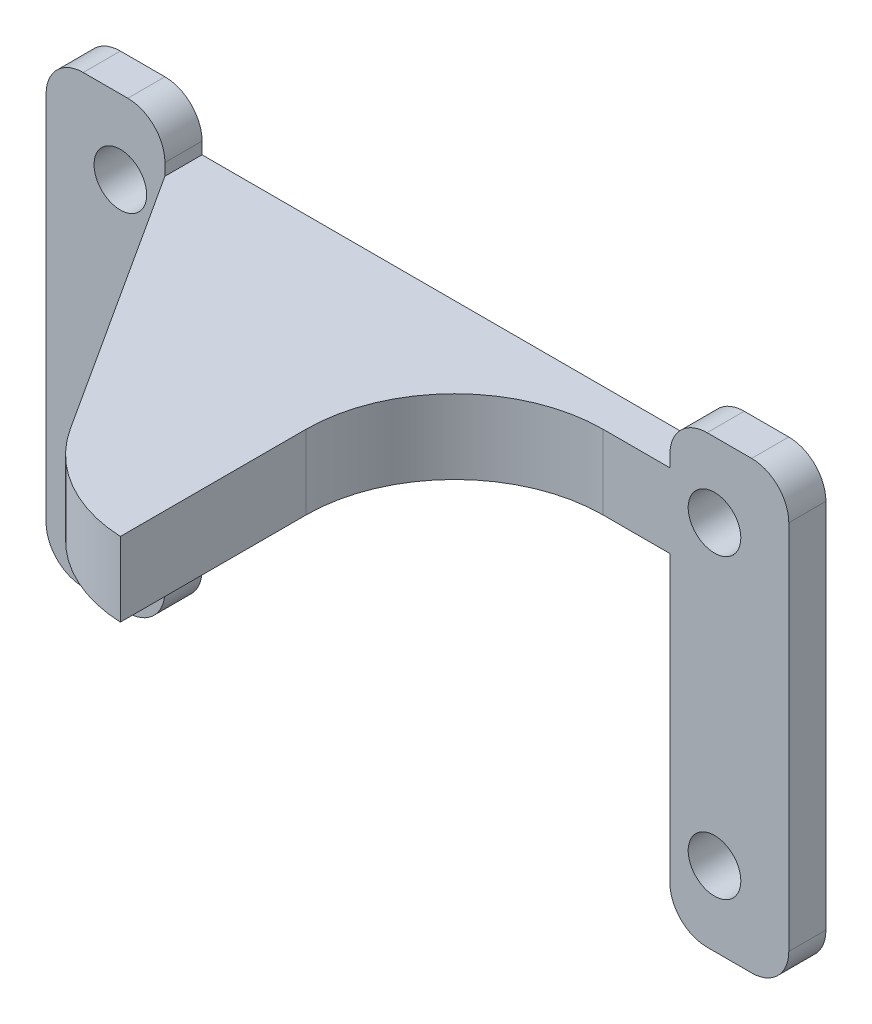
SolidWorks part; units mm, degrees
material "6061 Alloy"
ref_plane "Front" through (0, 0, 0) normal (0, 0, 1) x (1, 0, 0)
ref_plane "Top" through (0, 0, 0) normal (0, 1, 0) x (1, 0, 0)
ref_plane "Right" through (0, 0, 0) normal (1, 0, 0) x (0, 0, -1)
sketch "Sketch1" plane through (0, 0, 0) normal (0, 0, 1) x (1, 0, 0)
  line L1 (-31.75, -19.05) -> (31.75, -19.05)
  line L2 (-31.75, -19.05) -> (-31.75, 19.05)
  line L3 (-31.75, 19.05) -> (31.75, 19.05)
  line L4 (31.75, -19.05) -> (31.75, 19.05)
  line L5 (-31.75, -19.05) -> (31.75, 19.05) construction
  line L6 (-31.75, 19.05) -> (31.75, -19.05) construction
  point P0 (0, 0)
  dimension "D1" = 63.5
  dimension "D2" = 38.1
extrude "Boss-Extrude1" add sketch "Sketch1" along normal blind 3.175
sketch "Sketch2" plane through (0, 0, 3.175) normal (0, 0, 1) x (1, 0, 0)
  line L1 (-21.59, -19.05) -> (21.59, -19.05)
  line L2 (-21.59, -19.05) -> (-21.59, 19.05)
  line L3 (-21.59, 19.05) -> (21.59, 19.05)
  line L4 (21.59, -19.05) -> (21.59, 19.05)
  line L5 (-21.59, -19.05) -> (21.59, 19.05) construction
  line L6 (-21.59, 19.05) -> (21.59, -19.05) construction
  line L7 (-31.75, 19.05) -> (-31.75, -19.05) construction
  line L8 (31.75, 19.05) -> (-31.75, 19.05) construction
  point P0 (0, 0)
  dimension "D2" = 10.16
extrude "Cut-Extrude1" cut sketch "Sketch2" against normal through all
sketch "Sketch3" plane through (0, 0, 0) normal (1, 0, 0) x (0, 0, -1)
  line L5 (-31.75, 14.859) -> (0, 14.859)
  line L6 (-31.75, 14.859) -> (-31.75, 8.509)
  line L7 (-31.75, 8.509) -> (0, 8.509)
  line L8 (0, 14.859) -> (0, 8.509)
  line L9 (-31.75, 14.859) -> (0, 8.509) construction
  line L10 (-31.75, 8.509) -> (0, 14.859) construction
  line L11 (0, -19.05) -> (0, 19.05) construction
  point P6 (-15.875, 11.684)
  dimension "D1" = 6.35
  dimension "D2" = 31.75
  dimension "D3" = 4.191
extrude "Boss-Extrude2" add sketch "Sketch3" along normal mid plane 6.35 contours L6 L7 L5 region at (0, 11.684, 15.875)
sketch "Sketch4" plane through (0, 14.859, 0) normal (0, 1, 0) x (1, 0, 0)
  line L0 (-3.175, -31.75) -> (-21.59, -3.175)
  line L2 (-3.175, 0) -> (-3.175, -31.75)
  line L3 (31.75, -3.175) -> (21.59, -3.175) construction
  line L4 (31.75, 0) -> (21.59, 0) construction
  line L5 (-21.59, -3.175) -> (-21.59, 0)
  line L6 (-21.59, 0) -> (-3.175, 0)
  line L7 (-3.175, -31.75) -> (-3.175, 0) construction
  line L8 (3.175, -31.75) -> (3.175, 0) construction
  line L9 (31.75, 0) -> (3.175, 0)
  line L10 (31.75, 0) -> (31.75, -3.175)
  line L11 (31.75, -3.175) -> (3.175, -3.175)
  line L12 (3.175, 0) -> (3.175, -3.175)
  line L14 (-21.59, -3.175) -> (-31.75, -3.175) construction
  point P2 (-23.0003, -4.7558)
  point P6 (0, 0)
  point P20 (0, 0)
  point P24 (0, 0)
  point P26 (0, 0)
extrude "Boss-Extrude3" add sketch "Sketch4" against normal up to surface (6.35 mm away) up to face at (0, 8.509, 15.875)
fillet "Fillet1" radius 12.7 2 edges at (-3.175, 11.684, 31.75) (3.175, 11.684, 3.175)
sketch "Sketch5" plane through (0, 0, 3.175) normal (0, 0, 1) x (1, 0, 0)
  line L0 (-21.59, 19.05) -> (-31.75, 19.05) construction
  line L1 (-25.4, -12.7) -> (25.4, -12.7) construction
  line L2 (-25.4, -12.7) -> (-25.4, 12.7) construction
  line L3 (-25.4, 12.7) -> (25.4, 12.7) construction
  line L4 (25.4, -12.7) -> (25.4, 12.7) construction
  line L5 (-25.4, -12.7) -> (25.4, 12.7) construction
  line L6 (-25.4, 12.7) -> (25.4, -12.7) construction
  line L7 (-31.75, 19.05) -> (-31.75, -19.05) construction
  circle A0 centre (-25.4, 12.7) radius 2.25
  circle A1 centre (-25.4, -12.7) radius 2.25
  circle A2 centre (25.4, -12.7) radius 2.25
  circle A3 centre (25.4, 12.7) radius 2.25
  point P0 (0, 0)
  dimension "D3" = 4.5
  dimension "D1" = 6.35
  dimension "D2" = 6.35
extrude "Cut-Extrude2" cut sketch "Sketch5" against normal through all
fillet "Fillet2" radius 3.175 8 edges at (21.59, 19.05, 1.5875) (31.75, 19.05, 1.5875) (31.75, -19.05, 1.5875) (21.59, -19.05, 1.5875) (-31.75, -19.05, 1.5875) (-21.59, -19.05, 1.5875) (-21.59, 19.05, 1.5875) (-31.75, 19.05, 1.5875)
